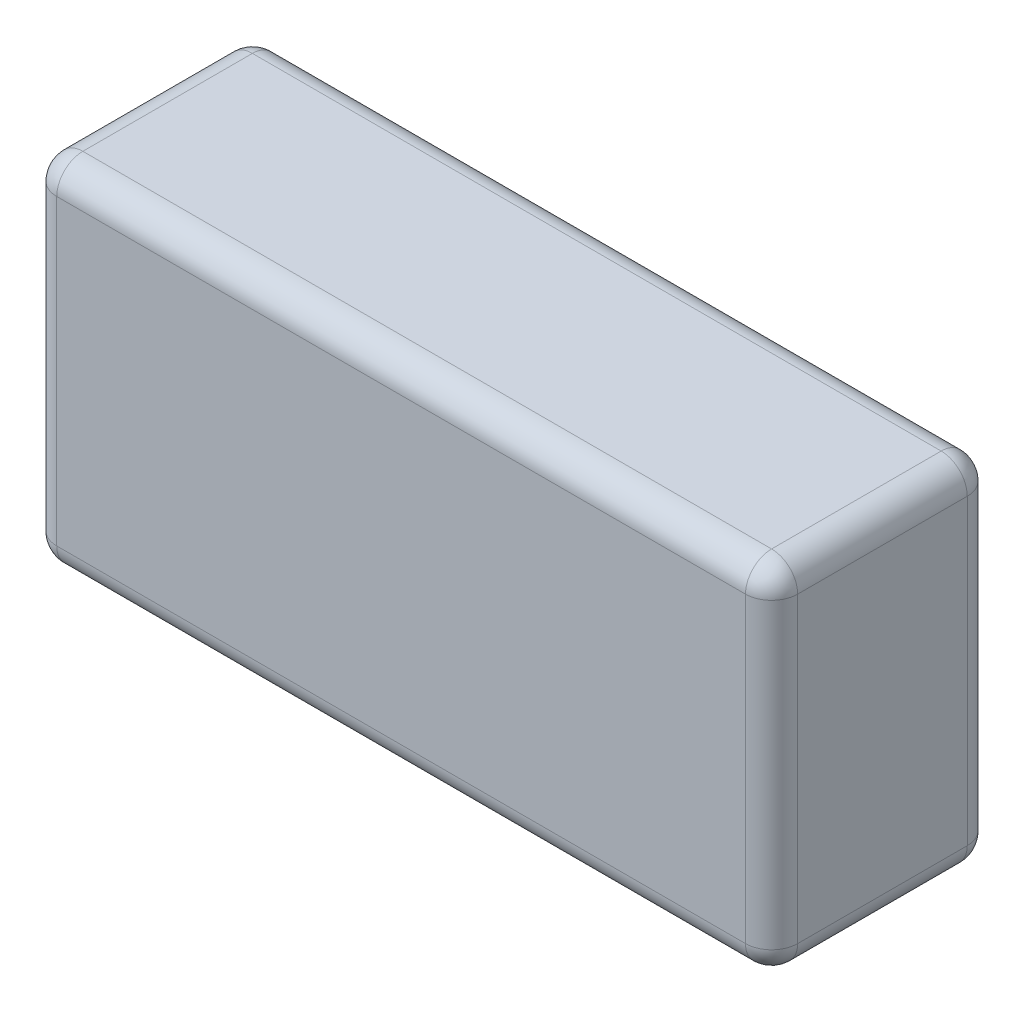
SolidWorks part; units mm, degrees
ref_plane "Front Plane" through (0, 0, 0) normal (0, 0, 1) x (1, 0, 0)
ref_plane "Top Plane" through (0, 0, 0) normal (0, 1, 0) x (1, 0, 0)
ref_plane "Right Plane" through (0, 0, 0) normal (1, 0, 0) x (0, 0, -1)
sketch "Sketch1" plane through (0, 0, 0) normal (0, 1, 0) x (1, 0, 0)
  line L1 (0, 0) -> (142, 0)
  line L2 (0, 0) -> (0, 42.5)
  line L3 (0, 42.5) -> (142, 42.5)
  line L4 (142, 0) -> (142, 42.5)
  dimension "D1" = 142
  dimension "D2" = 42.5
extrude "Boss-Extrude1" add sketch "Sketch1" along normal blind 68
sketch "Sketch2" plane through (0, 0, 0) normal (-1, 0, 0) x (0, 0, 1)
  circle A0 centre (-36.8168, 44.4533) radius 3.9822
  circle A1 centre (-36.8168, 19.2025) radius 4.4384
extrude "Boss-Extrude2" add sketch "Sketch2" along normal blind 10
fillet "Fillet1" radius 5 12 edges at (0, 0, -21.25) (71, 0, 0) (142, 0, -21.25) (71, 0, -42.5) (0, 68, -21.25) (142, 68, -21.25) (71, 68, -42.5) (0, 34, -42.5) (142, 34, -42.5) (142, 34, 0) (0, 34, 0) (71, 68, 0)
